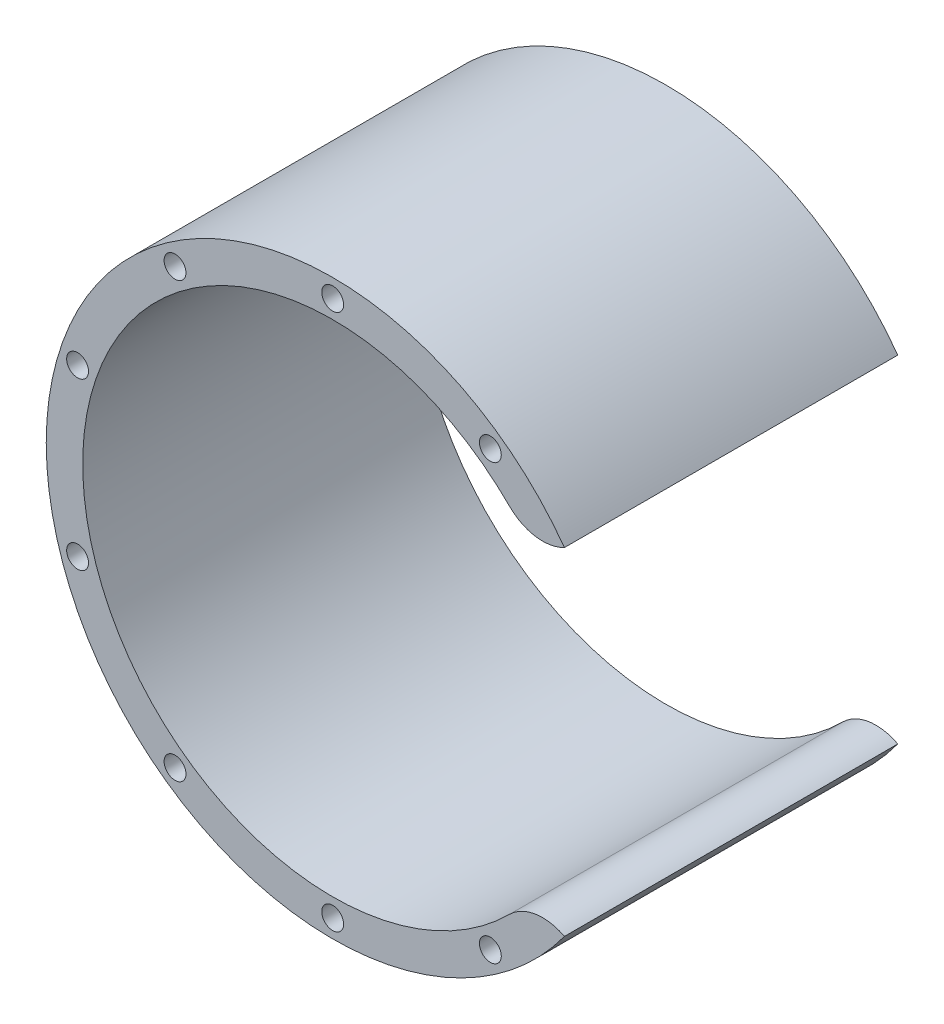
SolidWorks part; units mm, degrees
material "ABS"
ref_plane "Plan de face" through (0, 0, 0) normal (0, 0, 1) x (1, 0, 0)
ref_plane "Plan de dessus" through (0, 0, 0) normal (0, 1, 0) x (1, 0, 0)
ref_plane "Plan de droite" through (0, 0, 0) normal (1, 0, 0) x (0, 0, -1)
sketch "Esquisse1" plane through (0, 0, 0) normal (0, 0, 1) x (1, 0, 0)
  circle A0 centre (0, 0) radius 55
  circle A1 centre (0, 0) radius 48
  circle A2 centre (0, 0) radius 51.5 construction
  circle A3 centre (0, 51.5) radius 2.1
  circle A4 centre (30.2709, 41.6644) radius 2.1
  circle A5 centre (48.9794, 15.9144) radius 2.1
  circle A6 centre (48.9794, -15.9144) radius 2.1
  circle A7 centre (30.2709, -41.6644) radius 2.1
  circle A8 centre (0, -51.5) radius 2.1
  circle A9 centre (-30.2709, -41.6644) radius 2.1
  circle A10 centre (-48.9794, -15.9144) radius 2.1
  circle A11 centre (-48.9794, 15.9144) radius 2.1
  circle A12 centre (-30.2709, 41.6644) radius 2.1
  point P28 (0, 0)
  dimension "D1" = 110
  dimension "D2" = 96
  dimension "D3" = 103
  dimension "D4" = 4.2
  dimension "D5" = 10
extrude "Boss.-Extru.1" add sketch "Esquisse1" along normal blind 64
sketch "Esquisse3" plane through (0, 0, 64) normal (0, 0, 1) x (1, 0, 0)
  line L0 (0, 0) -> (60, 43.5926)
  line L1 (60, 43.5926) -> (60, -43.5926)
  line L2 (0, 0) -> (60, 0) construction
  line L3 (0, 0) -> (60, -43.5926)
  dimension "D1" = 60
  dimension "D2" = 36
extrude "Enlèv. mat.-Extru.1" cut sketch "Esquisse3" against normal through all
fillet "Congé1" radius 9 2 edges at (38.8328, -28.2137, 32) (38.8328, 28.2137, 32)
